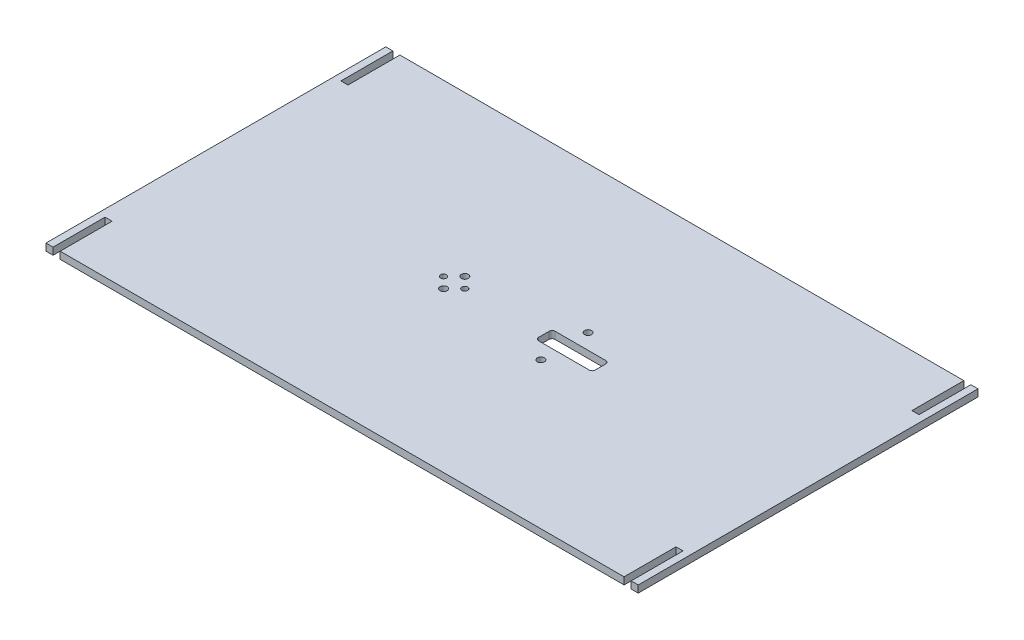
SolidWorks part; units mm, degrees
ref_plane "Front" through (0, 0, 0) normal (0, 0, 1) x (1, 0, 0)
ref_plane "Top" through (0, 0, 0) normal (0, 1, 0) x (1, 0, 0)
ref_plane "Right" through (0, 0, 0) normal (1, 0, 0) x (0, 0, -1)
sketch "Sketch1" plane through (0, 0, 0) normal (0, 1, 0) x (1, 0, 0)
  line L0 (478, 244) -> (484, 244)
  line L1 (0, 0) -> (478, 0)
  line L3 (0, 288) -> (478, 288)
  line L6 (484, 44) -> (478, 44)
  line L7 (478, 0) -> (478, 44)
  line L8 (478, 244) -> (478, 288)
  line L9 (0, 288) -> (0, 244)
  line L10 (-6, 244) -> (-6, 288)
  line L11 (0, 244) -> (-6, 244)
  line L12 (-6, 288) -> (-12, 288)
  line L14 (-6, 44) -> (0, 44)
  line L15 (0, 44) -> (0, 0)
  line L17 (-12, 288) -> (-12, 0)
  line L19 (-6, 44) -> (-6, 0)
  line L20 (-6, 0) -> (-12, 0)
  line L21 (484, 244) -> (484, 288)
  line L22 (484, 288) -> (490, 288)
  line L23 (490, 288) -> (490, 0)
  line L24 (490, 0) -> (484, 0)
  line L26 (484, 0) -> (484, 44)
  dimension "D1" = 6
  dimension "D2" = 6
  dimension "D3" = 6
  dimension "D4" = 288
  dimension "D5" = 478
  dimension "D6" = 200
  dimension "D7" = 12
  dimension "D8" = 490
  dimension "D9" = 12
  dimension "D10" = 44
  dimension "D11" = 6
extrude "Boss-Extrude1" add sketch "Sketch1" along normal blind 6
sketch "Sketch2" plane through (0, 6, 0) normal (0, 1, 0) x (1, 0, 0)
  line L0 (478, 288) -> (0, 288) construction
  line L1 (190, 153) -> (190, 135) construction
  line L2 (181, 144) -> (199, 144) construction
  line L3 (490, 0) -> (490, 288) construction
  line L13 (268.5, 137) -> (311.5, 137)
  line L14 (266, 139.5) -> (266, 148.5)
  line L15 (268.5, 151) -> (311.5, 151)
  line L16 (314, 139.5) -> (314, 148.5)
  circle A1 centre (190, 135) radius 3
  circle A2 centre (190, 153) radius 3
  circle A3 centre (181, 144) radius 2.5
  circle A4 centre (199, 144) radius 2.5
  circle A5 centre (283.5, 164) radius 3
  circle A6 centre (283.5, 124) radius 3
  arc A9 (314, 139.5) -> (311.5, 137) centre (311.5, 139.5) cw
  arc A10 (266, 139.5) -> (268.5, 137) centre (268.5, 139.5) ccw
  arc A11 (268.5, 151) -> (266, 148.5) centre (268.5, 148.5) ccw
  arc A12 (314, 148.5) -> (311.5, 151) centre (311.5, 148.5) ccw
  point P0 (190, 144)
  point P17 (266, 144)
  point P22 (0, 0)
  point P29 (0, 0)
  point P30 (0, 0)
  point P33 (314, 137)
  point P36 (266, 137)
  point P39 (266, 151)
  dimension "D1" = 9
  dimension "D4" = 6
  dimension "D5" = 5
  dimension "D7" = 18
  dimension "D8" = 144
  dimension "D9" = 14
  dimension "D10" = 43
  dimension "D3" = 9
  dimension "D11" = 20
  dimension "D12" = 6
  dimension "D13" = 40
  dimension "D14" = 76
  dimension "D15" = 2.5
  dimension "D16" = 17.5
  dimension "D2" = 300
  dimension "D6" = 18
extrude "Cut-Extrude1" cut sketch "Sketch2" against normal blind 6
